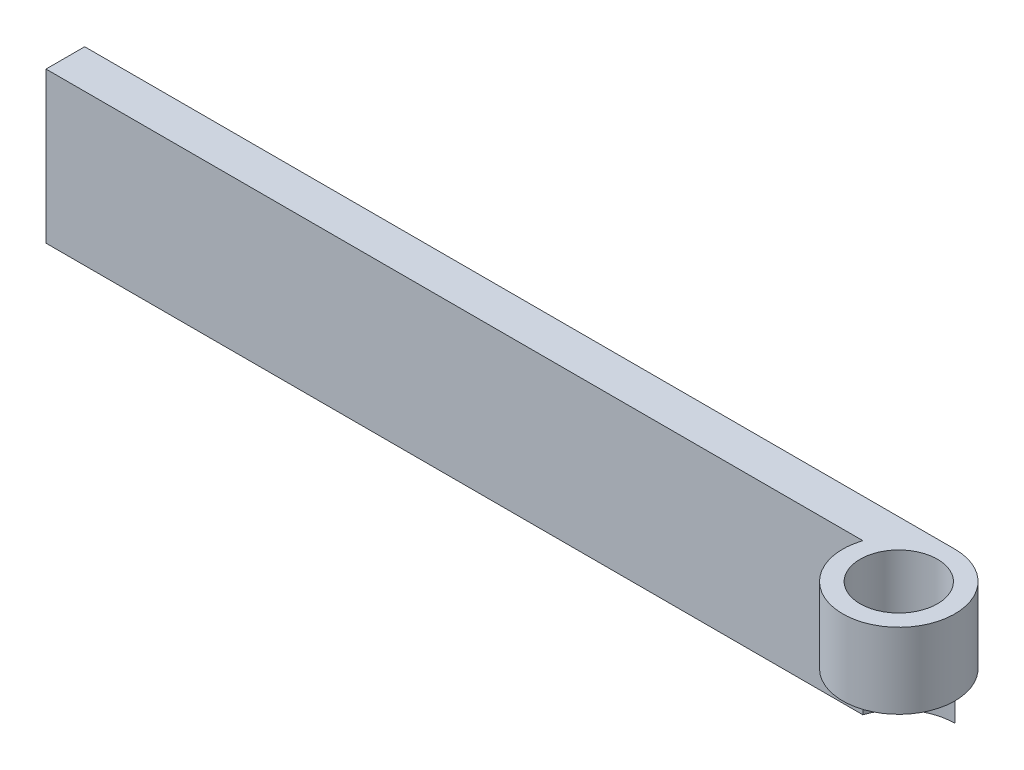
SolidWorks part; units mm, degrees
ref_plane "Alzado" through (0, 0, 0) normal (0, 0, 1) x (1, 0, 0)
ref_plane "Planta" through (0, 0, 0) normal (0, 1, 0) x (1, 0, 0)
ref_plane "Vista lateral" through (0, 0, 0) normal (1, 0, 0) x (0, 0, -1)
sketch "Croquis1" plane through (0, 0, 0) normal (0, 1, 0) x (1, 0, 0)
  circle A0 centre (0, 0) radius 2.9
  circle A1 centre (0, 0) radius 2
  dimension "D1" = 5.8
  dimension "D2" = 4
extrude "Saliente-Extruir1" add sketch "Croquis1" along normal blind 3.9
sketch "Croquis2" plane through (0, 0, 0) normal (0, -1, 0) x (1, 0, 0)
  line L0 (0, 3.7949) -> (0, 2.9) construction
  line L1 (0, -2.9) -> (-45, -2.9)
  line L2 (-45, -2.9) -> (-45, -0.9)
  line L3 (-45, -0.9) -> (-2.7568, -0.9)
  line L5 (0, -2.9) -> (0, -4.2431) construction
  circle A0 centre (0, 0) radius 2.9
  circle M5 centre (0, 0) radius 2.9
  dimension "D2" = 5.8
  dimension "D1" = 2
  dimension "D3" = 45
extrude "Saliente-Extruir2" add sketch "Croquis2" along normal blind 3.9 and the other way blind 3.9 contours L3 L2 L1 M5 region at (-23.5049, 0, -1.908)
